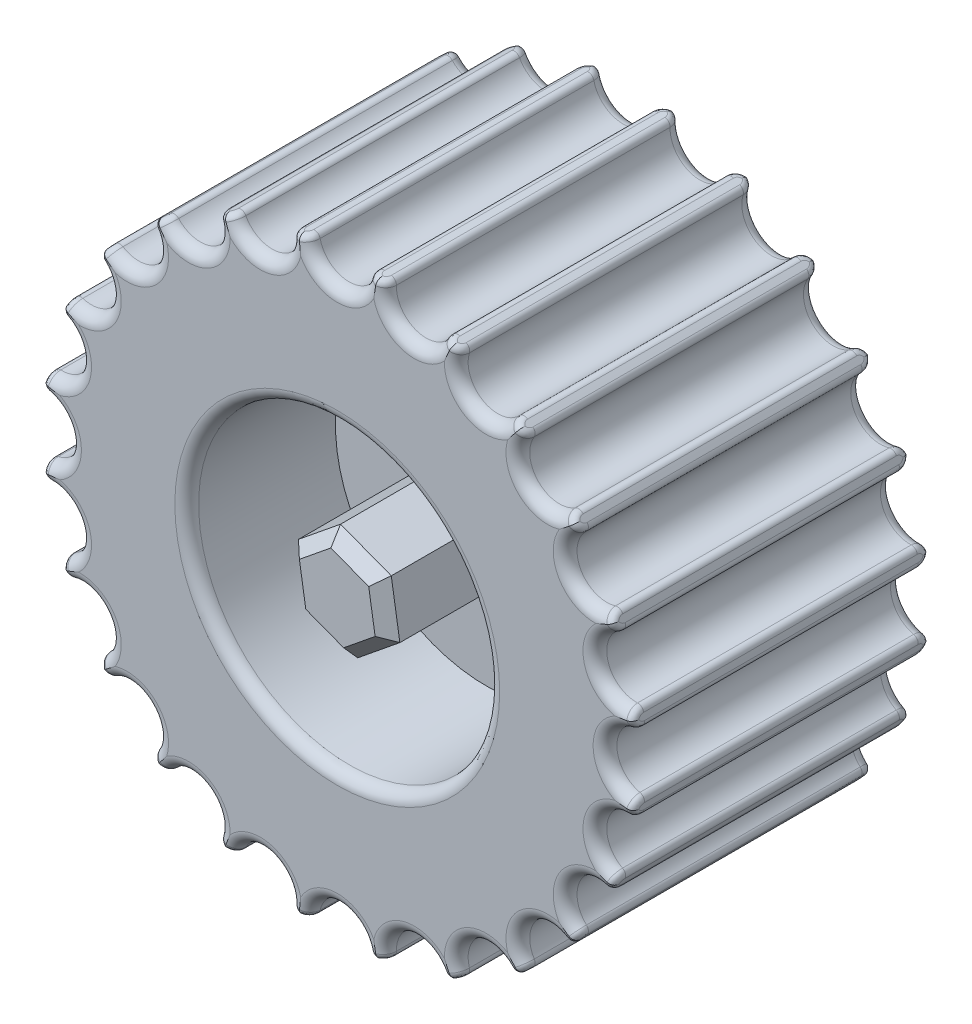
SolidWorks part; units mm, degrees
material "ABS"
ref_plane "Front Plane" through (0, 0, 0) normal (0, 0, 1) x (1, 0, 0)
ref_plane "Top Plane" through (0, 0, 0) normal (0, 1, 0) x (1, 0, 0)
ref_plane "Right Plane" through (0, 0, 0) normal (1, 0, 0) x (0, 0, -1)
sketch "Sketch1" plane through (0, 0, 0) normal (0, 0, 1) x (1, 0, 0)
  circle A0 centre (0, 0) radius 6.35
  dimension "D1" = 12.7
extrude "Boss-Extrude1" add sketch "Sketch1" along normal blind 6.35
sketch "Sketch3" plane through (0, 0, 6.35) normal (0, 0, 1) x (1, 0, 0)
  circle A0 centre (0, 0) radius 3.2131
  dimension "D1" = 6.4262
extrude "Cut-Extrude1" cut sketch "Sketch3" against normal blind 3.175
sketch "Sketch4" plane through (0, 0, 3.175) normal (0, 0, 1) x (1, 0, 0)
  line L1 (0.8991, 0.7306) -> (-0.1832, 1.1439)
  line L2 (-0.1832, 1.1439) -> (-1.0823, 0.4133)
  line L3 (-1.0823, 0.4133) -> (-0.8991, -0.7306)
  line L4 (-0.8991, -0.7306) -> (0.1832, -1.1439)
  line L5 (0.1832, -1.1439) -> (1.0823, -0.4133)
  line L6 (1.0823, -0.4133) -> (0.8991, 0.7306)
  circle A0 centre (0, 0) radius 1.0033 construction
  dimension "D1" = 2.0066
extrude "Boss-Extrude2" add sketch "Sketch4" along normal blind 3.175
sketch "Sketch5" plane through (0, 0, 0) normal (0, 0, -1) x (-1, 0, 0)
  circle A0 centre (0, 6.35) radius 0.635
  circle A1 centre (0, 0) radius 6.35 construction
  circle A2 centre (1.6435, 6.1336) radius 0.635
  circle A3 centre (3.175, 5.4993) radius 0.635
  circle A4 centre (4.4901, 4.4901) radius 0.635
  circle A5 centre (5.4993, 3.175) radius 0.635
  circle A6 centre (6.1336, 1.6435) radius 0.635
  circle A7 centre (6.35, 0) radius 0.635
  circle A8 centre (6.1336, -1.6435) radius 0.635
  circle A9 centre (5.4993, -3.175) radius 0.635
  circle A10 centre (4.4901, -4.4901) radius 0.635
  circle A11 centre (3.175, -5.4993) radius 0.635
  circle A12 centre (1.6435, -6.1336) radius 0.635
  circle A13 centre (0, -6.35) radius 0.635
  circle A14 centre (-1.6435, -6.1336) radius 0.635
  circle A15 centre (-3.175, -5.4993) radius 0.635
  circle A16 centre (-4.4901, -4.4901) radius 0.635
  circle A17 centre (-5.4993, -3.175) radius 0.635
  circle A18 centre (-6.1336, -1.6435) radius 0.635
  circle A19 centre (-6.35, 0) radius 0.635
  circle A20 centre (-6.1336, 1.6435) radius 0.635
  circle A21 centre (-5.4993, 3.175) radius 0.635
  circle A22 centre (-4.4901, 4.4901) radius 0.635
  circle A23 centre (-3.175, 5.4993) radius 0.635
  circle A24 centre (-1.6435, 6.1336) radius 0.635
  point P52 (0, 0)
  dimension "D1" = 1.27
  dimension "D2" = 24
extrude "Cut-Extrude2" cut sketch "Sketch5" against normal through all
fillet "Fillet1" radius 0.254 49 edges at (3.2131, 0, 6.35) (2.8575, 4.9493, 6.35) (4.0411, 4.0411, 6.35) (4.9493, 2.8575, 6.35) (5.5203, 1.4792, 6.35) (5.715, 0, 6.35) (5.5203, -1.4792, 6.35) (4.9493, -2.8575, 6.35) (4.0411, -4.0411, 6.35) (2.8575, -4.9493, 6.35) (1.4792, -5.5203, 6.35) (0, -5.715, 6.35) (-1.4792, -5.5203, 6.35) (-2.8575, -4.9493, 6.35) (-4.0411, -4.0411, 6.35) (-4.9493, -2.8575, 6.35) (-5.5203, -1.4792, 6.35) (-5.715, 0, 6.35) (-5.5203, 1.4792, 6.35) (-4.9493, 2.8575, 6.35) (-4.0411, 4.0411, 6.35) (-2.8575, 4.9493, 6.35) (-1.4792, 5.5203, 6.35) (0, 5.715, 6.35) (1.4792, 5.5203, 6.35) (0, 5.715, 0) (-1.4792, 5.5203, 0) (-2.8575, 4.9493, 0) (-4.0411, 4.0411, 0) (-4.9493, 2.8575, 0) (-5.5203, 1.4792, 0) (-5.715, 0, 0) (-5.5203, -1.4792, 0) (-4.9493, -2.8575, 0) (-4.0411, -4.0411, 0) (-2.8575, -4.9493, 0) (-1.4792, -5.5203, 0) (0, -5.715, 0) (1.4792, -5.5203, 0) (2.8575, -4.9493, 0) (4.0411, -4.0411, 0) (4.9493, -2.8575, 0) (5.5203, -1.4792, 0) (5.715, 0, 0) (5.5203, 1.4792, 0) (4.9493, 2.8575, 0) (4.0411, 4.0411, 0) (2.8575, 4.9493, 0) (1.4792, 5.5203, 0)
chamfer "Chamfer1" distance 0.254 angle 45 6 edges at (0.6327, -0.7786, 6.35) (-0.3579, -0.9373, 6.35) (-0.9907, -0.1586, 6.35) (-0.6327, 0.7786, 6.35) (0.3579, 0.9373, 6.35) (0.9907, 0.1586, 6.35)
fillet "Fillet2" radius 0.127 116 edges at (-5.8115, 2.5591, 0.0955) (-5.8193, 2.5413, 6.2762) (-5.9189, 2.2998, 6.2545) (-5.9388, 2.2479, 3.175) (-5.1105, 3.769, 0.0738) (-4.9511, 3.976, 0.0955) (-4.9161, 4.0192, 3.175) (-4.9633, 3.9608, 6.2762) (-5.122, 3.7534, 6.2545) (-3.9608, 4.9633, 0.0738) (-3.7534, 5.122, 0.0955) (-3.7084, 5.1547, 3.175) (-3.769, 5.1105, 6.2762) (-3.976, 4.9511, 6.2545) (-4.0192, 4.9161, 3.175) (-2.5413, 5.8193, 0.0738) (-2.2998, 5.9189, 0.0955) (-2.5591, 5.8115, 6.2545) (-2.6099, 5.7889, 3.175) (-0.9485, 6.2788, 0.0738) (-0.6895, 6.3125, 0.0955) (-0.6342, 6.3183, 3.175) (-0.7088, 6.3103, 6.2762) (-0.9678, 6.2758, 6.2545) (-1.0227, 6.2671, 3.175) (0.9678, 6.2758, 0.0955) (1.0227, 6.2671, 3.175) (0.9485, 6.2788, 6.2762) (0.6895, 6.3125, 6.2545) (0.6342, 6.3183, 3.175) (2.2479, 5.9388, 3.175) (2.5591, 5.8115, 0.0955) (2.6099, 5.7889, 3.175) (2.5413, 5.8193, 6.2762) (3.769, 5.1105, 0.0738) (3.976, 4.9511, 0.0955) (3.9608, 4.9633, 6.2762) (3.7084, 5.1547, 3.175) (4.9633, 3.9608, 0.0738) (5.122, 3.7534, 0.0955) (5.1105, 3.769, 6.2762) (4.9511, 3.976, 6.2545) (4.9161, 4.0192, 3.175) (5.9189, 2.2998, 0.0955) (5.9388, 2.2479, 3.175) (5.9118, 2.3179, 6.2762) (5.8115, 2.5591, 6.2545) (5.7889, 2.6099, 3.175) (6.2788, 0.9485, 0.0738) (6.3125, 0.6895, 0.0955) (6.3182, 0.6342, 3.175) (6.3103, 0.7088, 6.2762) (6.2758, 0.9678, 6.2545) (6.3103, -0.7088, 0.0738) (6.2758, -0.9678, 0.0955) (6.2788, -0.9485, 6.2762) (6.3182, -0.6342, 3.175) (5.9118, -2.3179, 0.0738) (5.8115, -2.5591, 0.0955) (5.9189, -2.2998, 6.2545) (5.9388, -2.2479, 3.175) (5.1105, -3.769, 0.0738) (4.9511, -3.976, 0.0955) (4.9633, -3.9608, 6.2762) (5.122, -3.7534, 6.2545) (5.1547, -3.7084, 3.175) (3.9608, -4.9633, 0.0738) (3.7534, -5.122, 0.0955) (3.7084, -5.1547, 3.175) (3.769, -5.1105, 6.2762) (3.976, -4.9511, 6.2545) (4.0192, -4.9161, 3.175) (2.5413, -5.8193, 0.0738) (2.2998, -5.9189, 0.0955) (2.2479, -5.9388, 3.175) (2.3179, -5.9118, 6.2762) (2.5591, -5.8115, 6.2545) (0.9485, -6.2788, 0.0738) (0.6342, -6.3183, 3.175) (0.9678, -6.2758, 6.2545) (1.0227, -6.2671, 3.175) (-0.7088, -6.3103, 0.0738) (-0.9485, -6.2788, 6.2762) (-0.6342, -6.3182, 3.175) (-2.3179, -5.9118, 0.0738) (-2.5591, -5.8115, 0.0955) (-2.6099, -5.7889, 3.175) (-2.2998, -5.9189, 6.2545) (-2.2479, -5.9388, 3.175) (-3.976, -4.9511, 0.0955) (-4.0192, -4.9161, 3.175) (-3.9608, -4.9633, 6.2762) (-3.7534, -5.122, 6.2545) (-3.7084, -5.1547, 3.175) (-4.9633, -3.9608, 0.0738) (-5.122, -3.7534, 0.0955) (-5.1547, -3.7084, 3.175) (-5.1105, -3.769, 6.2762) (-4.9161, -4.0192, 3.175) (-5.8193, -2.5413, 0.0738) (-5.9189, -2.2998, 0.0955) (-5.9388, -2.2479, 3.175) (-5.8115, -2.5591, 6.2545) (-5.7889, -2.6099, 3.175) (-6.2788, -0.9485, 0.0738) (-6.3125, -0.6895, 0.0955) (-6.3183, -0.6342, 3.175) (-6.3103, -0.7088, 6.2762) (-6.2758, -0.9678, 6.2545) (-6.2671, -1.0227, 3.175) (-6.3103, 0.7088, 0.0738) (-6.2758, 0.9678, 0.0955) (-6.2671, 1.0227, 3.175) (-6.2788, 0.9485, 6.2762) (-6.3125, 0.6895, 6.2545) (-6.3182, 0.6342, 3.175)
